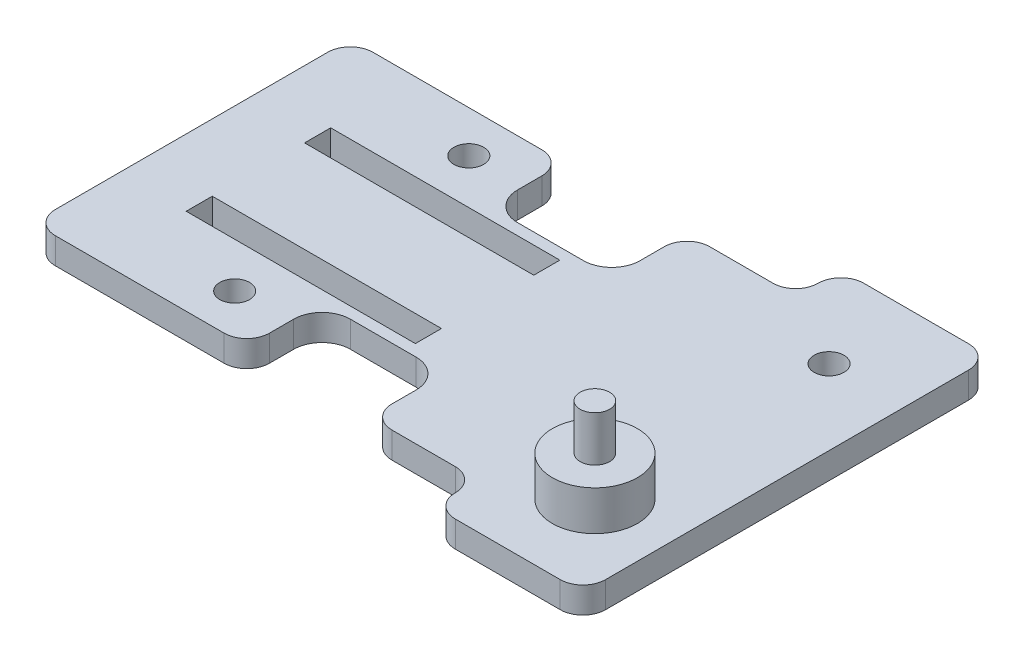
SolidWorks part; units mm, degrees
other "下垫片"
ref_plane "前视基准面" through (0, 0, 0) normal (0, 0, 1) x (1, 0, 0)
ref_plane "上视基准面" through (0, 0, 0) normal (0, 1, 0) x (1, 0, 0)
ref_plane "右视基准面" through (0, 0, 0) normal (1, 0, 0) x (0, 0, -1)
other "Configuration Table"
sketch "草图1" plane through (0, 0, 0) normal (0, 1, 0) x (1, 0, 0)
  line L0 (-89.3251, 0) -> (102.0425, 0) construction
  line L1 (0, 56.7239) -> (0, -62.578) construction
  line L2 (-48.2, -8.1375) -> (-7.8, -8.1375)
  line L3 (-48.2, 12.7375) -> (-7.8, 12.7375)
  line L4 (-48.2, 12.7375) -> (-48.2, 8.1375)
  line L5 (-48.2, 8.1375) -> (-7.8, 8.1375)
  line L6 (-7.8, 12.7375) -> (-7.8, 8.1375)
  line L7 (-48.2, 12.7375) -> (-7.8, 8.1375) construction
  line L8 (-48.2, 8.1375) -> (-7.8, 12.7375) construction
  line L9 (-7.8, -12.7375) -> (-7.8, -8.1375)
  line L10 (-48.2, -12.7375) -> (-7.8, -12.7375)
  line L11 (-48.2, -12.7375) -> (-48.2, -8.1375)
  line L14 (-22.25, -26.5375) -> (-22.25, -14.7375)
  line L15 (-22.25, -14.7375) -> (-0.65, -14.7375)
  line L16 (-0.65, -26.5375) -> (-0.65, -14.7375)
  line L17 (-22.25, -26.5375) -> (-0.65, -14.7375) construction
  line L18 (-22.25, -14.7375) -> (-0.65, -26.5375) construction
  line L19 (-22.25, 14.7375) -> (-0.65, 14.7375)
  line L20 (-0.65, 26.5375) -> (-0.65, 14.7375)
  line L22 (-22.25, 26.5375) -> (-22.25, 14.7375)
  line L23 (-22.25, 30.0095) -> (-0.65, 30.0095)
  line L25 (-22.25, -26.5375) -> (-22.25, -30.0095)
  line L26 (-22.25, -30.0095) -> (-0.65, -30.0095)
  line L27 (-0.65, -26.5375) -> (-0.65, -30.0095)
  line L28 (-0.65, 26.5375) -> (-0.65, 30.0095)
  line L30 (-22.25, 26.5375) -> (-22.25, 30.0095)
  circle A0 centre (-31.75, 20.6375) radius 2.625
  circle A4 centre (31.75, 20.6375) radius 2.625
  circle A5 centre (31.75, -20.6375) radius 2.625
  circle A6 centre (-31.75, -20.6375) radius 2.625
  point P13 (-28, 10.4375)
  point P22 (-11.45, -20.6375)
  point P35 (-28, 10.4375)
  dimension "D5" = 5.25
  dimension "D11" = 5.25
  dimension "D1" = 40.4
  dimension "D2" = 31.75
  dimension "D3" = 4.6
  dimension "D4" = 20.6375
  dimension "D6" = 9.5
  dimension "D7" = 21.6
  dimension "D8" = 11.8
  dimension "D9" = 0
  dimension "D10" = 32.4
  dimension "D12" = 4.6
  dimension "D13" = 40.4
  dimension "D14" = 28
  dimension "D15" = 10.4375
  dimension "D16" = 2
sketch "草图3" plane through (0, 0, 0) normal (0, 1, 0) x (1, 0, 0)
  line L0 (-40, 28) -> (-60, 28)
  line L1 (-40, -28) -> (18.5, -28)
  line L3 (-40, 28) -> (18.5, 28)
  line L5 (-40, -28) -> (40, 28) construction
  line L6 (-40, 28) -> (40, -28) construction
  line L7 (-60, 28) -> (-60, -28)
  line L8 (-60, -28) -> (-40, -28)
  line L10 (45, 28) -> (45, -28)
  line L12 (45, -28) -> (45, -36)
  line L13 (45, -36) -> (18.5, -36)
  line L14 (18.5, -36) -> (18.5, -28)
  line L15 (-45.7746, 0) -> (58.2399, 0) construction
  line L16 (45, 28) -> (45, 36)
  line L17 (45, 36) -> (18.5, 36)
  line L18 (18.5, 36) -> (18.5, 28)
  point P0 (0, 0)
  dimension "D1" = 56
  dimension "D2" = 80
  dimension "D3" = 20
  dimension "D4" = 5
  dimension "D5" = 26.5
  dimension "D6" = 8
extrude "凸台-拉伸1" add sketch "草图3" along normal blind 4.6
extrude "切除-拉伸1" cut sketch "草图1" along normal up to surface (4.6 mm away) up to face at (5.5, 4.6, 0)
sketch "草图5" plane through (0, 4.6, 0) normal (0, 1, 0) x (1, 0, 0)
  circle A0 centre (31.75, -20.6375) radius 7.5
  dimension "D1" = 15
extrude "凸台-拉伸2" add sketch "草图5" along normal blind 7
sketch "草图6" plane through (0, 11.6, 0) normal (0, 1, 0) x (1, 0, 0)
  circle A0 centre (31.75, -20.6375) radius 2.6
  dimension "D1" = 5.2
extrude "凸台-拉伸3" add sketch "草图6" along normal blind 8
fillet "圆角1" radius 5 4 edges at (-0.65, 2.3, 14.7375) (-22.25, 2.3, 14.7375) (-0.65, 2.3, -14.7375) (-22.25, 2.3, -14.7375)
fillet "圆角2" radius 4 12 edges at (-0.65, 2.3, 28) (-22.25, 2.3, 28) (-0.65, 2.3, -28) (-22.25, 2.3, -28) (-60, 2.3, 28) (-60, 2.3, -28) (18.5, 2.3, -28) (18.5, 2.3, -36) (45, 2.3, -36) (45, 2.3, 36) (18.5, 2.3, 36) (18.5, 2.3, 28)
sketch "草图7" plane through (0, 0, 0) normal (0, -1, 0) x (1, 0, 0)
  line L0 (-31.75, 20.6375) -> (31.75, 20.6375) construction
  line L1 (0, 27.9483) -> (0, -23.2551) construction
